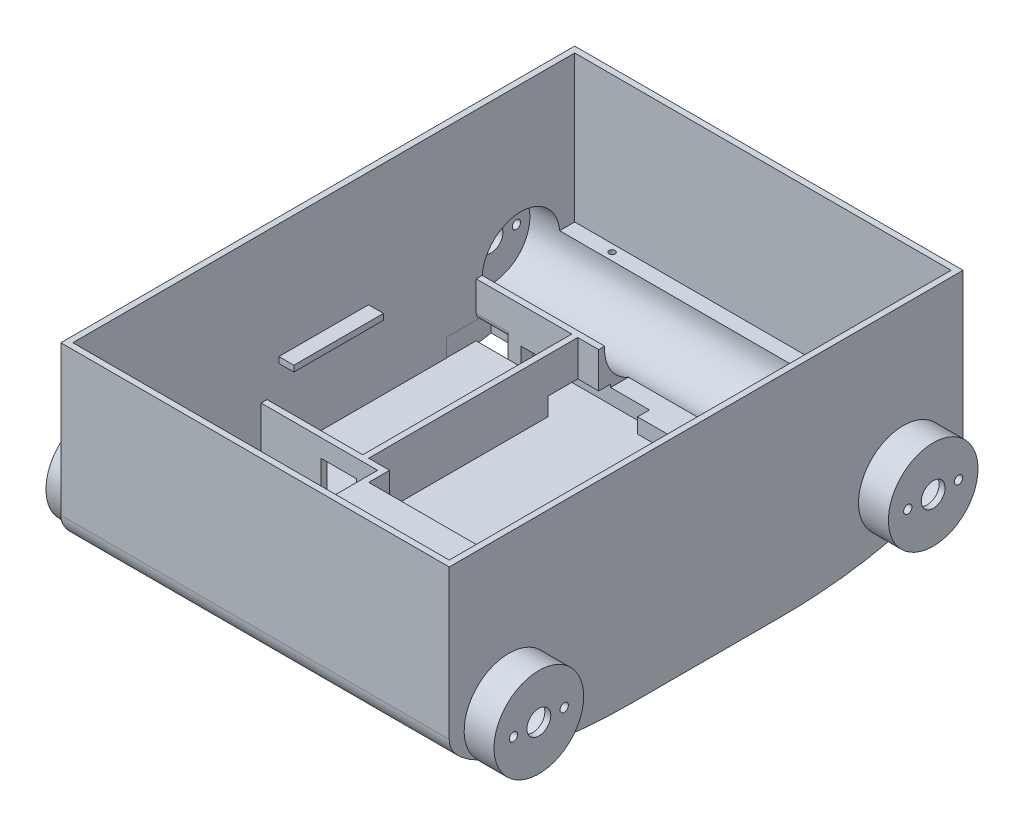
SolidWorks part; units mm, degrees
ref_plane "Спереди" through (0, 0, 0) normal (0, 0, 1) x (1, 0, 0)
ref_plane "Сверху" through (0, 0, 0) normal (0, 1, 0) x (1, 0, 0)
ref_plane "Справа" through (0, 0, 0) normal (1, 0, 0) x (0, 0, -1)
sketch "Эскиз1" plane through (0, 0, 0) normal (0, 1, 0) x (1, 0, 0)
  line L1 (-65, 86) -> (65, 86)
  line L2 (-65, 86) -> (-65, -86)
  line L3 (-65, -86) -> (65, -86)
  line L4 (65, 86) -> (65, -86)
  dimension "D1" = 130
  dimension "D2" = 65
  dimension "D3" = 172
  dimension "D4" = 86
extrude "Бобышка-Вытянуть1" add sketch "Эскиз1" along normal blind 35 and the other way blind 35
sketch "Эскиз2" plane through (65, 0, 0) normal (1, 0, 0) x (0, 0, -1)
  line L0 (-86, -15) -> (86, -15) construction
  line L1 (-86, -35) -> (-86, 35) construction
  line L2 (86, -35) -> (86, 35) construction
  line L3 (-86, -35) -> (86, -35) construction
  line L4 (-25, -35) -> (25, -35)
  line L5 (-86, -40.7424) -> (-86, -15)
  line L7 (-86, -40.7424) -> (86, -40.7424)
  line L8 (86, -40.7424) -> (86, -15)
  ellipse E0 centre (-25, -15) end of major axis (-86, -15) minor radius 20 (-86, -15) -> (-25, -35) ccw
  ellipse E1 centre (25, -15) end of major axis (-36, -15) minor radius 20 (86, -15) -> (25, -35) cw
  point P10 (-25, -15)
  point P11 (25, -15)
  dimension "D1" = 20
  dimension "D2" = 50
  dimension "D3" = 25
  dimension "D4" = 25
  dimension "D5" = 25
extrude "Вырез-Вытянуть1" cut sketch "Эскиз2" against normal blind 130
sketch "Эскиз3" plane through (0, 35, 0) normal (0, 1, 0) x (1, 0, 0)
  line L0 (-65, 86) -> (-65, -86) construction
  line L1 (-63, 84) -> (63, 84)
  line L2 (-63, 84) -> (-63, -84)
  line L3 (-63, -84) -> (63, -84)
  line L4 (63, 84) -> (63, -84)
  line L5 (65, -86) -> (65, 86) construction
  line L6 (-65, -86) -> (65, -86) construction
  line L7 (65, 86) -> (-65, 86) construction
  dimension "D1" = 2
  dimension "D2" = 2
  dimension "D3" = 2
  dimension "D4" = 2
extrude "Вырез-Вытянуть2" cut sketch "Эскиз3" against normal blind 49
sketch "Эскиз4" plane through (0, 0, 0) normal (1, 0, 0) x (0, 0, -1)
  line L0 (-86, -15) -> (86, -15) construction
  circle A0 centre (-66, -15) radius 13
  circle A1 centre (66, -15) radius 13
  ellipse E0 centre (25, -15) end of major axis (86, -15) minor radius 20 (25, -35) -> (86, -15) ccw construction
  point P10 (-66, -15)
  point P11 (66, -15)
  dimension "D3" = 26
  dimension "D4" = 26
  dimension "D1" = 20
  dimension "D2" = 20
extrude "Вырез-Вытянуть3" cut sketch "Эскиз4" against normal blind 63 and the other way blind 63
sketch "Эскиз7" plane through (65, 0, 0) normal (1, 0, 0) x (0, 0, -1)
  line L0 (-86, -15) -> (86, -15) construction
  line L1 (-86, -15) -> (-86, 35) construction
  line L2 (86, -15) -> (86, 35) construction
  line L3 (-86, 35) -> (86, 35) construction
  circle A0 centre (-74.5, -15) radius 1.4
  circle A1 centre (-66, -15) radius 4
  circle A2 centre (-57.5, -15) radius 1.4
  circle A3 centre (57.5, -15) radius 1.4
  circle A4 centre (66, -15) radius 4
  circle A5 centre (74.5, -15) radius 1.4
  point P8 (-66, -15)
  point P9 (66, -15)
  point P10 (-74.5, -15)
  point P11 (-57.5, -15)
  point P12 (74.5, -15)
  point P13 (57.5, -15)
  dimension "D8" = 2.8
  dimension "D9" = 2.8
  dimension "D10" = 2.8
  dimension "D11" = 2.8
  dimension "D12" = 8
  dimension "D13" = 8
  dimension "D1" = 50
  dimension "D2" = 20
  dimension "D3" = 20
  dimension "D4" = 8.5
  dimension "D5" = 8.5
  dimension "D6" = 8.5
  dimension "D7" = 8.5
sketch "Эскиз8" plane through (65, 0, 0) normal (1, 0, 0) x (0, 0, -1)
  line L0 (-86, -15) -> (-86, 35) construction
  circle A0 centre (-66, -15) radius 15
  circle A1 centre (66, -15) radius 15
  dimension "D1" = 20
  dimension "D2" = 30
  dimension "D3" = 20
extrude "Бобышка-Вытянуть3" add sketch "Эскиз8" along normal blind 10
mirror "Зеркальное отражение2" about plane through (0, 0, 0) normal (1, 0, 0) of "Бобышка-Вытянуть3"
extrude "Вырез-Вытянуть6" cut sketch "Эскиз7" along normal blind 32 and the other way blind 160
sketch "Эскиз9" plane through (63, 0, 0) normal (-1, 0, 0) x (0, 0, 1)
  circle A0 centre (-66, -15) radius 13
  circle A1 centre (66, -15) radius 13
  dimension "D1" = 26
  dimension "D2" = 26
extrude "Вырез-Вытянуть7" cut sketch "Эскиз9" against normal blind 10 and the other way blind 136
sketch "Эскиз10" plane through (0, -14, 0) normal (0, 1, 0) x (1, 0, 0)
  line L1 (-63, 51.0385) -> (-31, 51.0385)
  line L2 (-63, 51.0385) -> (-63, -18.9615)
  line L3 (-63, -18.9615) -> (-31, -18.9615)
  line L4 (-31, 51.0385) -> (-31, -18.9615)
  line L7 (63, 53.0385) -> (-63, 53.0385) construction
  line L8 (-63, 53.0385) -> (-63, -53.0385) construction
  line L9 (63, -53.0385) -> (63, 53.0385) construction
  line L10 (31, 51.0385) -> (63, 51.0385)
  line L11 (31, 51.0385) -> (31, -18.9615)
  line L12 (31, -18.9615) -> (63, -18.9615)
  line L13 (63, 51.0385) -> (63, -18.9615)
  dimension "D1" = 70
  dimension "D2" = 2
  dimension "D3" = 2
  dimension "D4" = 32
  dimension "D5" = 0
  dimension "D6" = 70
  dimension "D7" = 32
  dimension "D8" = 0
extrude "Вырез-Вытянуть8" cut sketch "Эскиз10" against normal blind 18
sketch "Эскиз11" plane through (0, -14, 0) normal (0, 1, 0) x (1, 0, 0)
  line L0 (63, 53.0385) -> (-63, 53.0385) construction
  line L1 (-29, 51.0385) -> (29, 51.0385)
  line L2 (-29, 51.0385) -> (-29, -18.9615)
  line L3 (-29, -18.9615) -> (29, -18.9615)
  line L4 (29, 51.0385) -> (29, -18.9615)
  line L7 (-31, -18.9615) -> (-31, 51.0385) construction
  line L8 (31, 51.0385) -> (31, -18.9615) construction
  line L9 (-63, -18.9615) -> (-31, -18.9615) construction
  dimension "D1" = 2
  dimension "D2" = 0
  dimension "D3" = 2
  dimension "D4" = 2
  dimension "D5" = 58
  dimension "D6" = 70
extrude "Вырез-Вытянуть9" cut sketch "Эскиз11" against normal blind 18
sketch "Эскиз13" plane through (0, -14, 0) normal (0, 1, 0) x (1, 0, 0)
  line L0 (29, 51.0385) -> (-29, 51.0385) construction
  line L1 (-22, 51.0385) -> (22, 51.0385)
  line L2 (-22, 51.0385) -> (-22, 67.0385)
  line L3 (-22, 67.0385) -> (22, 67.0385)
  line L4 (22, 51.0385) -> (22, 67.0385)
  line L8 (-63, -53.0385) -> (63, -53.0385) construction
  line L9 (-29, -18.9615) -> (29, -18.9615) construction
  line L10 (-8, -25.9615) -> (-22, -25.9615)
  line L11 (-22, -18.9615) -> (-22, -25.9615)
  line L12 (-22, -18.9615) -> (22, -18.9615)
  line L14 (-22, -67.0385) -> (22, -67.0385)
  line L16 (22, -18.9615) -> (22, -25.9615)
  line L17 (-8, -25.9615) -> (-8, -45.9615)
  line L18 (8, -25.9615) -> (8, -45.9615)
  line L19 (22, -67.0385) -> (22, -45.9615)
  line L20 (-22, -67.0385) -> (-22, -45.9615)
  line L21 (-8, -45.9615) -> (-22, -45.9615)
  line L22 (8, -25.9615) -> (22, -25.9615)
  line L23 (8, -45.9615) -> (22, -45.9615)
  dimension "D1" = 44
  dimension "D2" = 22
  dimension "D3" = 14
  dimension "D4" = 8
  dimension "D5" = 16
  dimension "D6" = 22
  dimension "D7" = 22
  dimension "D8" = 20
  dimension "D9" = 7
  dimension "D10" = 7.077
  dimension "D11" = 16
  dimension "D12" = 22
extrude "Вырез-Вытянуть11" cut sketch "Эскиз13" against normal blind 13
sketch "Эскиз14" plane through (0, 0, -51.0385) normal (0, 0, 1) x (1, 0, 0)
  line L0 (-63, -32) -> (-63, -14) construction
  line L1 (-9, -26) -> (-48, -26)
  line L2 (-9, -26) -> (-9, -32)
  line L3 (-9, -32) -> (-48, -32)
  line L4 (-48, -26) -> (-48, -32)
  line L5 (-29, -32) -> (-29, -14) construction
  line L6 (29, -32) -> (-29, -32) construction
  line L7 (-31, -32) -> (-31, -14) construction
  line L9 (-63.0555, -32) -> (-52.3555, -32)
  line L10 (-63.0555, -32) -> (-63.0555, -26)
  line L11 (-63.0555, -26) -> (-52.3555, -26)
  line L12 (-52.3555, -32) -> (-52.3555, -26)
  dimension "D1" = 15
  dimension "D2" = 20
  dimension "D3" = 6
  dimension "D4" = 0
  dimension "D5" = 17
  dimension "D6" = 10.7
  dimension "D7" = 6
extrude "Вырез-Вытянуть12" cut sketch "Эскиз14" against normal blind 4 and the other way blind 10
mirror "Зеркальное отражение4" about plane through (0, 0, 0) normal (1, 0, 0) of "Вырез-Вытянуть12"
sketch "Эскиз15" plane through (63, 0, 0) normal (-1, 0, 0) x (0, 0, 1)
  line L0 (18.9615, -14) -> (-51.0385, -14) construction
  line L1 (-15, -3.5) -> (15, -3.5)
  line L2 (-15, -3.5) -> (-15, -5.5)
  line L3 (-15, -5.5) -> (15, -5.5)
  line L4 (15, -3.5) -> (15, -5.5)
  dimension "D1" = 30
  dimension "D2" = 15
  dimension "D3" = 2
  dimension "D4" = 8.5
extrude "Бобышка-Вытянуть4" add sketch "Эскиз15" along normal blind 5
mirror "Зеркальное отражение3" about plane through (0, 0, 0) normal (1, 0, 0) of "Бобышка-Вытянуть4"
sketch "Эскиз16" plane through (0, -14, 0) normal (0, 1, 0) x (1, 0, 0)
  line L0 (-63, 78.9615) -> (63, 78.9615) construction
  line L1 (-63, 84) -> (-63, 78.9615) construction
  circle A0 centre (-48, 81.5015) radius 1
  point P6 (-63, 81.4807)
  dimension "D1" = 2.54
  dimension "D3" = 2
  dimension "D2" = 15
extrude "Вырез-Вытянуть13" cut sketch "Эскиз16" against normal blind 5
mirror "Зеркальное отражение5" about plane through (0, 0, 0) normal (0, 0, 1) of "Вырез-Вытянуть13"
mirror "Зеркальное отражение6" about plane through (0, 0, 0) normal (1, 0, 0) of "Зеркальное отражение5"
sketch "Эскиз17" plane through (0, -32, 0) normal (0, 1, 0) x (1, 0, 0)
  line L1 (-52.3555, 51.0385) -> (-63.0555, 51.0385)
  line L2 (-52.3555, 51.0385) -> (-52.3555, 56.0385)
  line L3 (-52.3555, 56.0385) -> (-63.0555, 56.0385)
  line L4 (-63.0555, 51.0385) -> (-63.0555, 56.0385)
  dimension "D1" = 5
extrude "Вырез-Вытянуть14" cut sketch "Эскиз17" against normal through all and the other way blind 3
mirror "Зеркальное отражение10" about plane through (0, 0, 0) normal (1, 0, 0) of "Вырез-Вытянуть14"
fillet "Скругление17" radius 2 4 edges at (-57.7055, -29, -55.0385) (-57.6778, -26, -51.0385) (57.6778, -26, -51.0385) (57.7055, -29, -55.0385)
sketch "Эскиз18" plane through (0, -14, 0) normal (0, 1, 0) x (1, 0, 0)
  line L1 (-8, -25.9615) -> (8, -25.9615)
  line L2 (-8, -25.9615) -> (-8, -45.9615)
  line L3 (-8, -45.9615) -> (8, -45.9615)
  line L4 (8, -25.9615) -> (8, -45.9615)
extrude "Бобышка-Вытянуть5" add sketch "Эскиз18" against normal blind 2
sketch "Эскиз19" plane through (0, -14, 0) normal (0, 1, 0) x (1, 0, 0)
  line L0 (-63, 84) -> (-63, -84) construction
  line L1 (-63, -20.9615) -> (-24, -20.9615)
  line L2 (-63, -20.9615) -> (-63, -51.0385)
  line L3 (-63, -51.0385) -> (-24, -51.0385)
  line L4 (-24, -20.9615) -> (-24, -51.0385)
  line L5 (24, -20.9615) -> (63, -20.9615)
  line L6 (24, -20.9615) -> (24, -51.0385)
  line L7 (24, -51.0385) -> (63, -51.0385)
  line L8 (63, -20.9615) -> (63, -51.0385)
  line L9 (-63, -18.9615) -> (-31, -18.9615) construction
  line L10 (-63, -53.0385) -> (-22, -53.0385) construction
  line L11 (-22, -45.9615) -> (-22, -61) construction
  line L12 (22, -53.0385) -> (22, -45.9615) construction
  line L13 (-29, -18.9615) -> (29, -18.9615) construction
  line L14 (22, -53.0385) -> (63, -53.0385) construction
  line L15 (63, -84) -> (63, 84) construction
  dimension "D1" = 0
  dimension "D2" = 2
  dimension "D3" = 2
  dimension "D4" = 2
  dimension "D5" = 2
  dimension "D6" = 2
  dimension "D7" = 2
  dimension "D8" = 0
extrude "Вырез-Вытянуть15" cut sketch "Эскиз19" against normal blind 18
sketch "Эскиз20" plane through (0, -32, 0) normal (0, 1, 0) x (1, 0, 0)
  line L0 (-24, -20.9615) -> (-63, -20.9615) construction
  line L1 (-31, -18.9615) -> (-43, -18.9615)
  line L2 (-31, -18.9615) -> (-31, -20.9615)
  line L3 (-31, -20.9615) -> (-43, -20.9615)
  line L4 (-43, -18.9615) -> (-43, -20.9615)
  dimension "D1" = 12
extrude "Вырез-Вытянуть16" cut sketch "Эскиз20" along normal blind 12
sketch "Эскиз21" plane through (0, -32, 0) normal (0, 1, 0) x (1, 0, 0)
  line L0 (63, -20.9615) -> (24, -20.9615) construction
  line L1 (63, -18.9615) -> (51, -18.9615)
  line L2 (63, -18.9615) -> (63, -20.9615)
  line L3 (63, -20.9615) -> (51, -20.9615)
  line L4 (51, -18.9615) -> (51, -20.9615)
  dimension "D1" = 12
extrude "Вырез-Вытянуть17" cut sketch "Эскиз21" along normal blind 12
sketch "Эскиз22" plane through (0, 0, 18.9615) normal (0, 0, -1) x (-1, 0, 0)
  line L0 (29, -32) -> (-29, -32) construction
  line L1 (24, -20) -> (29, -20)
  line L2 (24, -20) -> (24, -32)
  line L3 (24, -32) -> (29, -32)
  line L4 (29, -20) -> (29, -32)
  line L5 (29, -32) -> (29, -14) construction
  line L6 (22, -27) -> (22, -14) construction
  line L7 (29, -14) -> (22, -14) construction
  dimension "D1" = 0
  dimension "D2" = 0
  dimension "D3" = 2
  dimension "D4" = 6
extrude "Вырез-Вытянуть18" cut sketch "Эскиз22" against normal blind 9
